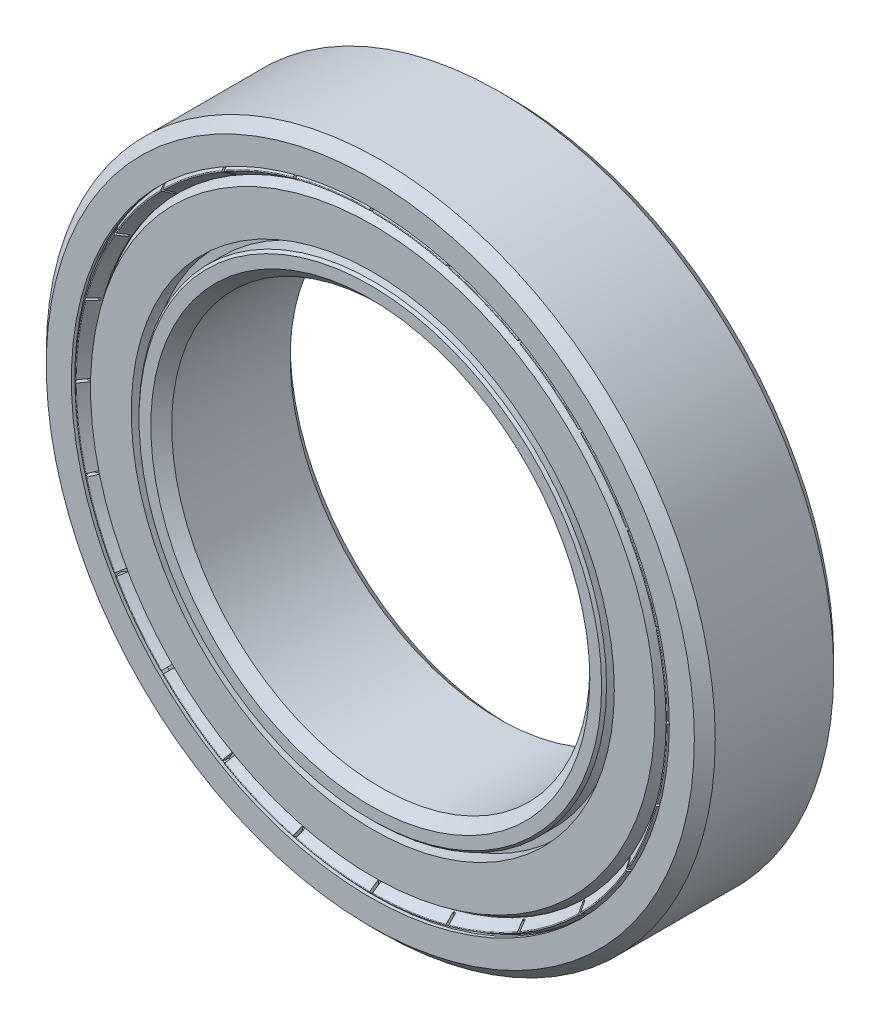
SolidWorks part; units mm, degrees
ref_plane "Front Plane" through (0, 0, 0) normal (0, 0, 1) x (1, 0, 0)
ref_plane "Top Plane" through (0, 0, 0) normal (0, 1, 0) x (1, 0, 0)
ref_plane "Right Plane" through (0, 0, 0) normal (1, 0, 0) x (0, 0, -1)
sketch "Sketch1" plane through (0, 0, 0) normal (0, 0, 1) x (1, 0, 0)
  circle A0 centre (0, 0) radius 7.5
  circle A1 centre (0, 0) radius 12
  dimension "OD" = 24
  dimension "ID" = 15
sketch "Sketch2" plane through (0, 0, 0) normal (1, 0, 0) x (0, 0, -1)
  line L0 (-2.5, 12) -> (2.5, 12)
  line L1 (-2.5, 7.5) -> (-2.5, -7.5) construction
  line L2 (2.5, 12) -> (2.5, -12) construction
  line L3 (-2.5, 0) -> (2.5, 0) construction
  line L6 (0, 12) -> (0, 7.5) construction
  circle A0 centre (0, 9.75) radius 1.575 construction
  point P8 (0, 12)
  dimension "Approx. Ball Dia." = 3.15
  dimension "Width" = 5
  dimension "For Shaft Diameter" = 15
  dimension "For Housing ID" = 24
sketch "Sketch3" plane through (0, 0, 0) normal (1, 0, 0) x (0, 0, -1)
  line L0 (0, 0) -> (0, 15) construction
  line L1 (-2.5, 7.5) -> (-2.5, -7.5) construction
  line L2 (2.125, 12) -> (-2.125, 12)
  line L3 (-2.125, 12) -> (-2.5, 11.625)
  line L4 (-2.5, 11.625) -> (-2.5, 10.7262)
  line L5 (-2.5, 10.7262) -> (-2.375, 10.7262)
  line L6 (-2.375, 10.7262) -> (-2.375, 11.0256)
  line L7 (-2.375, 11.0256) -> (-2.2866, 11.114)
  line L8 (-2.2866, 11.114) -> (-0.7875, 11.114)
  line L10 (-2.5, 12) -> (2.5, 12) construction
  line L12 (-2.375, 11.0256) -> (-2.375, 11.325) construction
  line L13 (2.2866, 11.114) -> (0.7875, 11.114)
  line L14 (2.375, 11.0256) -> (2.2866, 11.114)
  line L15 (2.375, 10.7262) -> (2.375, 11.0256)
  line L16 (2.5, 10.7262) -> (2.375, 10.7262)
  line L17 (2.5, 11.625) -> (2.5, 10.7262)
  line L18 (2.125, 12) -> (2.5, 11.625)
  line L19 (2.125, 7.5) -> (-2.125, 7.5)
  line L20 (-2.125, 7.5) -> (-2.5, 7.875)
  line L21 (-2.5, 7.875) -> (-2.5, 8.2976)
  line L22 (-2.5, 8.2976) -> (-2.4116, 8.386)
  line L23 (-2.4116, 8.386) -> (-0.7875, 8.386)
  line L25 (2.4116, 8.386) -> (0.7875, 8.386)
  line L26 (2.5, 8.2976) -> (2.4116, 8.386)
  line L27 (2.5, 7.875) -> (2.5, 8.2976)
  line L28 (2.125, 7.5) -> (2.5, 7.875)
  circle A2 centre (0, 9.75) radius 1.575 construction
  arc A3 (-0.7875, 11.114) -> (0.7875, 11.114) centre (0, 9.75) cw
  arc A4 (-0.7875, 8.386) -> (0.7875, 8.386) centre (0, 9.75) ccw
  point P5 (0, 11.325)
  point P31 (0, 12)
  point P37 (0, 7.5)
  dimension "D1" = 45
  dimension "D2" = 0.125
  dimension "D3" = 1.575
  dimension "D4" = 0.375
revolve "Revolve1" add sketch "Sketch3" angle 360 about L3
sketch "Sketch4" plane through (0, 0, 0) normal (1, 0, 0) x (0, 0, -1)
  line L0 (0, 11.325) -> (0, 8.175)
  line L1 (0, 12) -> (0, 7.5) construction
  circle A0 centre (0, 9.75) radius 1.575 construction
  arc A1 (0, 8.175) -> (0, 11.325) centre (0, 9.75) cw
revolve "Revolve2" add sketch "Sketch4" angle 360 about L6
pattern_circular "CirPattern1" count 12 over 360 about axis through (0, 0, 2.5) along (0, 0, -1) of bodies 106
sketch "Sketch5" plane through (0, 0, 0) normal (1, 0, 0) x (0, 0, -1)
  line L0 (-1.575, 9.75) -> (-1.575, 8.386) construction
  line L1 (-2.4116, 8.386) -> (-0.7875, 8.386) construction
  line L3 (-1.575, 8.386) -> (-1.8539, 8.386)
  line L4 (-1.8539, 8.386) -> (-1.8539, 8.6649)
  line L5 (-1.8539, 8.6649) -> (-2.4116, 8.6649)
  line L6 (-2.4116, 8.6649) -> (-2.4116, 10.1253)
  line L7 (-2.4116, 10.1253) -> (-1.8539, 10.4473)
  line L8 (-1.8539, 10.4473) -> (-1.575, 10.4473)
  line L9 (-1.575, 10.4473) -> (-1.575, 8.386)
  line L10 (0, 9.75) -> (0, 12) construction
  line L11 (1.8539, 10.4473) -> (1.575, 10.4473)
  line L12 (2.4116, 10.1253) -> (1.8539, 10.4473)
  line L13 (2.4116, 8.6649) -> (2.4116, 10.1253)
  line L14 (1.8539, 8.6649) -> (2.4116, 8.6649)
  line L15 (1.8539, 8.386) -> (1.8539, 8.6649)
  line L16 (1.575, 8.386) -> (1.8539, 8.386)
  line L17 (1.575, 10.4473) -> (1.575, 8.386)
  line L18 (-2.4116, 10.1253) -> (-2.1327, 10.1253) construction
  line L19 (-2.1327, 10.1253) -> (-1.8539, 10.1253) construction
  line L20 (-1.8539, 10.1253) -> (-1.575, 10.1253) construction
  line L21 (-1.8539, 10.4473) -> (-1.8539, 10.7262) construction
  circle A0 centre (0, 9.75) radius 1.575 construction
  dimension "D1" = 30
revolve "Revolve3" add sketch "Sketch5" angle 360 about L3
sketch "Sketch6" plane through (0, 0, 0) normal (1, 0, 0) x (0, 0, -1)
  line L0 (-2.0406, 10.7262) -> (-2.2812, 10.7262)
  line L1 (-2.2812, 10.7262) -> (-2.5, 10.5999)
  line L2 (-2.5, 10.5999) -> (-2.1156, 10.3307)
  line L4 (-2.4116, 10.1253) -> (-1.8539, 10.4473) construction
  line L5 (-2.0406, 10.3395) -> (-2.0406, 10.7262)
  line L6 (-2.5, 10.7262) -> (-2.375, 10.7262) construction
  line L7 (-2.1156, 10.3307) -> (-2.0906, 10.3307)
  line L8 (-2.0906, 10.3307) -> (-2.0406, 10.3395)
  line L9 (-2.5, 11.625) -> (-2.5, -11.625) construction
  line L11 (-2.0906, 10.3307) -> (-2.0656, 10.3307) construction
  line L12 (-2.0656, 10.3307) -> (-2.0406, 10.3307) construction
  point P27 (-2.1609, 10.7262)
  dimension "D1" = 30
  dimension "D3" = 10
  dimension "D2" = 35
  dimension "D4" = 0.025
  dimension "D5" = 0.2188
revolve "Revolve4" add sketch "Sketch6" angle 360 about L3
fillet "Fillet1" radius 0.025 1 edges at (10.5999, 0, 2.5)
sketch "Sketch7" plane through (0, 0, 0) normal (0, 0, 1) x (1, 0, 0)
  line L0 (-0.05, 10.7262) -> (-0.05, 10.8262)
  line L1 (-0.05, 10.7262) -> (0.05, 10.7262) construction
  line L2 (-0.05, 10.7262) -> (-0.05, 10.3307)
  line L3 (-0.05, 10.3307) -> (0.05, 10.3307) construction
  line L4 (0.05, 10.7262) -> (0.05, 10.3307)
  line L5 (-0.05, 10.8262) -> (0.05, 10.8262)
  line L6 (0.05, 10.8262) -> (0.05, 10.7262)
  line L7 (-0.05, 10.3307) -> (-0.05, 10.2307)
  line L8 (-0.05, 10.2307) -> (0.05, 10.2307)
  line L9 (0.05, 10.2307) -> (0.05, 10.3307)
  dimension "D1" = 0.1
extrude "Cut-Extrude1" cut sketch "Sketch7" along normal through all from vertex starting at point (0, 10.7262, 2.1609)
pattern_circular "CirPattern2" count 24 over 360 about axis through (0, 0, 2.5) along (0, 0, -1) of "Cut-Extrude1"
mirror "Mirror1" about plane through (0, 0, 0) normal (0, 0, 1) of bodies 120
equation "\"Approx. Ball Dia.@Sketch2\"=( \"OD@Sketch1\" - \"ID@Sketch1\" )  * .5 * .7"
equation "\"D2@Sketch3\"=\"Width@Sketch2\"*.025"
equation "\"D3@Sketch3\"=\"Approx. Ball Dia.@Sketch2\"*.5"
equation "\"D4@Sketch3\"=\"Width@Sketch2\"*.075"
equation "\"Approx No of Balls\"= ( pi * \"OD@Sketch1\" ) * .5 / \"Approx. Ball Dia.@Sketch2\""
equation "\"D1@CirPattern1\"=\"Approx No of Balls\""
equation "\"D4@Sketch6\"=\"D2@Sketch3\"*.2"
equation "\"D1@CirPattern2\"=\"Approx No of Balls\"*2"
equation "\"D5@Sketch6\"=\"D2@Sketch3\"*1.75"
equation "\"D1@Fillet1\"=\"d4@sketch6\""
